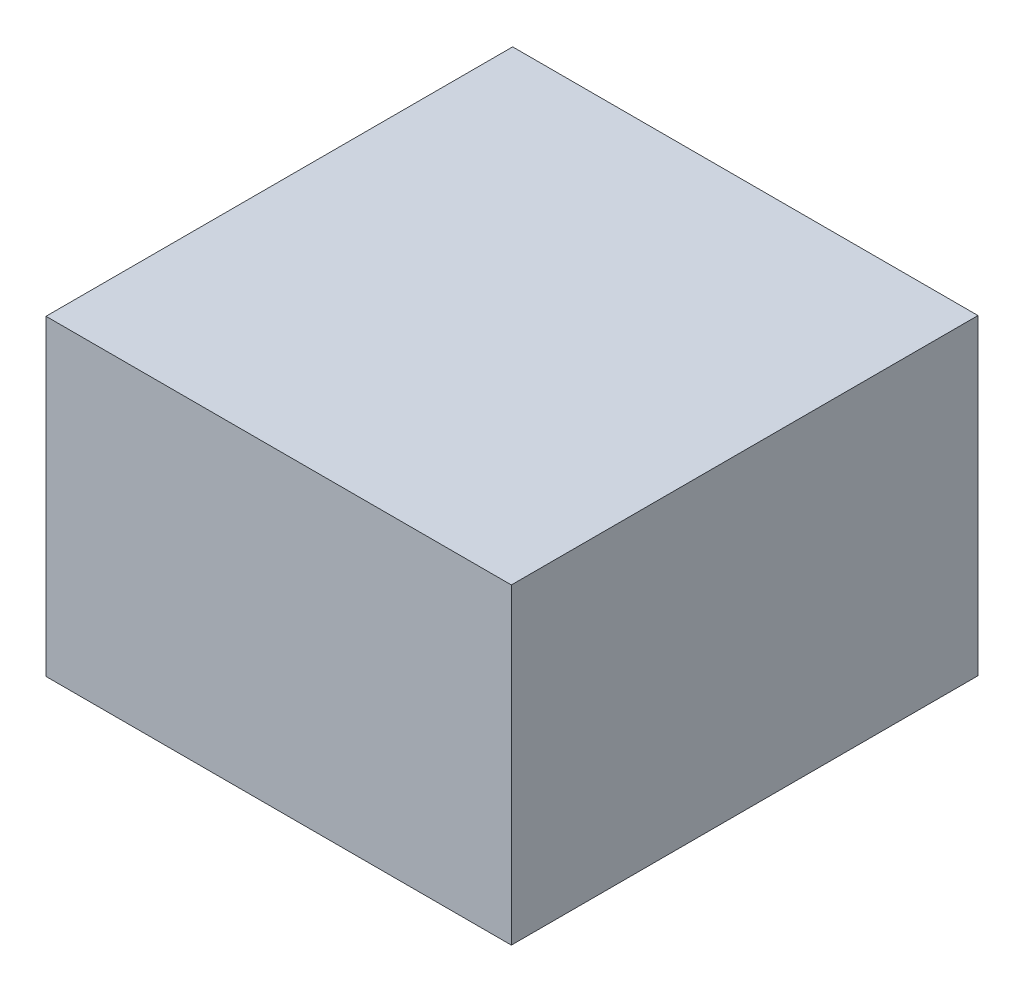
SolidWorks part; units mm, degrees
ref_plane "Front Plane" through (0, 0, 0) normal (0, 0, 1) x (1, 0, 0)
ref_plane "Top Plane" through (0, 0, 0) normal (0, 1, 0) x (1, 0, 0)
ref_plane "Right Plane" through (0, 0, 0) normal (1, 0, 0) x (0, 0, -1)
sketch "Sketch2" plane through (0, 0, 0) normal (0, 0, 1) x (1, 0, 0)
  line L1 (-457.2, 0) -> (457.2, 0)
  line L2 (-457.2, 0) -> (-457.2, 609.6)
  line L3 (-457.2, 609.6) -> (457.2, 609.6)
  line L4 (457.2, 0) -> (457.2, 609.6)
  dimension "D1" = 914.4
  dimension "D2" = 609.6
extrude "Boss-Extrude1" add sketch "Sketch2" along normal blind 914.4
shell "Shell2" thickness 2.54 removed face at (-457.2, 304.8, 457.2) outward yes
sketch "Sketch3" plane through (0, 609.6, 0) normal (0, -1, 0) x (1, 0, 0)
  line L0 (375.4397, 755.9837) -> (305.5897, 635)
  line L1 (375.4397, 755.9837) -> (298.45, 800.4337)
  line L2 (305.5897, 635) -> (228.6, 679.45)
  line L3 (298.45, 800.4337) -> (228.6, 679.45)
  line L4 (459.74, 916.94) -> (459.74, -2.54) construction
  dimension "D1" = 88.9
  dimension "D2" = 139.7
  dimension "D3" = 635
  dimension "D4" = 228.6
  dimension "D5" = 30
extrude "Boss-Extrude2" add sketch "Sketch3" along normal blind 76.2
sketch "Sketch4" plane through (351.3605, 0, 608.5742) normal (-0.5, 0, -0.866) x (-0.866, 0, 0.5)
  line L0 (115.7134, 533.4) -> (52.8516, 596.2618)
  line L1 (141.7516, 533.4) -> (52.8516, 533.4) construction
  line L2 (52.8516, 533.4) -> (52.8516, 609.6) construction
  line L7 (52.8516, 596.2618) -> (52.8516, 533.4)
  line L8 (52.8516, 533.4) -> (115.7134, 533.4)
  dimension "D1" = 45
  dimension "D2" = 88.9
extrude "Cut-Extrude1" cut sketch "Sketch4" against normal up to next
sketch "Sketch5" plane through (-281.0743, 324.5567, 162.2783) normal (0.6124, -0.7071, -0.3536) x (-0.7906, -0.5477, -0.2739)
  line L0 (-673.2161, -357.5302) -> (-742.0778, -301.3049) construction
  line L1 (-830.4318, -409.516) -> (-742.0778, -301.3049) construction
  circle A0 centre (-751.824, -383.5231) radius 12.7
  dimension "D1" = 25.4
  dimension "D2" = 69.85
  dimension "D3" = 44.45
extrude "Cut-Extrude2" cut sketch "Sketch5" against normal blind 50.8
equation "\"W\"=36"
equation "\"D1@Sketch2\"=\"W\""
equation "\"H\"= 24"
equation "\"D2@Sketch2\"=\"H\""
equation "\"L\"=36"
equation "\"D1@Boss-Extrude1\"=\"L\""
